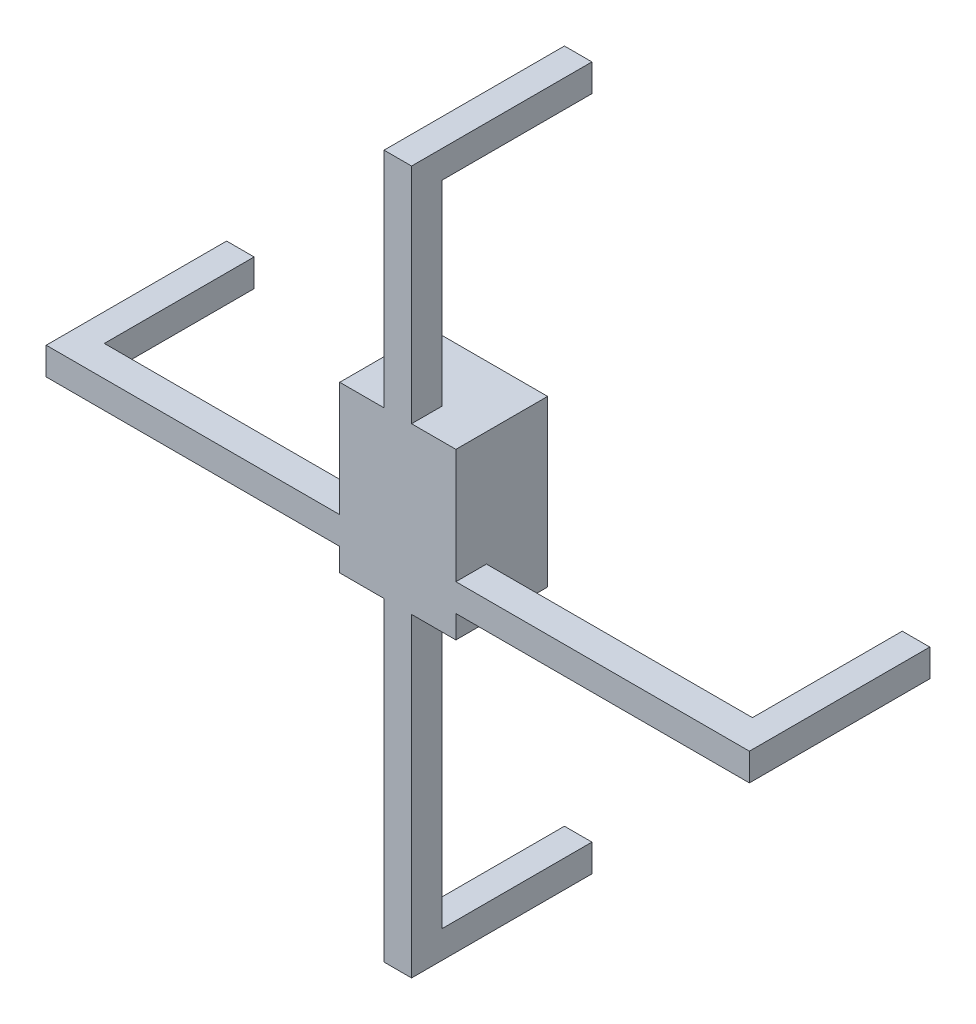
SolidWorks part; units mm, degrees
ref_plane "Front Plane" through (0, 0, 0) normal (0, 0, 1) x (1, 0, 0)
ref_plane "Top Plane" through (0, 0, 0) normal (0, 1, 0) x (1, 0, 0)
ref_plane "Right Plane" through (0, 0, 0) normal (1, 0, 0) x (0, 0, -1)
sketch "Sketch6" plane through (0, 0, 0) normal (1, 0, 0) x (0, 0, -1)
  line L0 (-4, 2.5) -> (1, 2.5) construction
  line L1 (27.5, 55.5) -> (1, 55.5)
  line L3 (-4, -55) -> (27.5, -55)
  line L4 (27.5, -55) -> (27.5, -50.5)
  line L5 (27.5, -50.5) -> (1, -50.5)
  line L8 (27.5, 60) -> (27.5, 55.5)
  line L10 (1, -50.5) -> (1, 55.5)
  line L12 (-4, -55) -> (-4, 60)
  line L22 (-4, 60) -> (27.5, 60)
  dimension "D3" = 5
  dimension "D6" = 4.5
ref_plane "Plane2" through (0, 2.5, 0) normal (0, 1, 0) x (1, 0, 0)
sketch "Sketch8" plane through (0, 2.5, 0) normal (0, 1, 0) x (1, 0, 0)
  line L0 (-57.5, -4) -> (57.5, -4)
  line L1 (-53, 1) -> (53, 1)
  line L3 (57.5, -4) -> (57.5, 27.5)
  line L11 (53, 27.5) -> (57.5, 27.5)
  line L12 (0, -4) -> (0, 1) construction
  line L13 (53, 27.5) -> (53, 1)
  line L14 (-53, 27.5) -> (-53, 1)
  line L15 (-53, 27.5) -> (-57.5, 27.5)
  line L16 (-57.5, -4) -> (-57.5, 27.5)
  point P0 (10.2551, -12.9586)
  point P2 (-10.2551, -12.9586)
  dimension "D2" = 4.5
  dimension "D9" = 5
extrude "Boss-Extrude7" add sketch "Sketch8" along normal blind 2.25 and the other way blind 2.25
sketch "Sketch10" plane through (0, 0, -1) normal (0, 0, -1) x (-1, 0, 0)
  line L2 (6.5, 20.5) -> (-6.5, 20.5)
  line L3 (6.5, 20.5) -> (6.5, -2.5)
  line L4 (-6.5, 20.5) -> (-6.5, -2.5)
  line L7 (6.5, -2.5) -> (6.5, -3.5)
  line L8 (-6.5, -2.5) -> (-6.5, -3.5)
  line L10 (9.5, -2.5) -> (9.5, -3.5)
  line L11 (9.5, 23.5) -> (9.5, -2.5)
  line L12 (9.5, 23.5) -> (-9.5, 23.5)
  line L13 (-9.5, 23.5) -> (-9.5, -2.5)
  line L14 (-9.5, -2.5) -> (-9.5, -3.5)
  line L15 (9.5, -3.5) -> (6.5, -3.5)
  line L16 (-9.5, -3.5) -> (-6.5, -3.5)
  point P6 (0, 1)
  dimension "D1" = 23
  dimension "D2" = 13
  dimension "D3" = 3
extrude "Boss-Extrude10" add sketch "Sketch10" along normal blind 10
extrude "Boss-Extrude12" add sketch "Sketch6" along normal blind 2.25 and the other way blind 2.25
sketch "Sketch11" plane through (0, 0, -1) normal (0, 0, 1) x (1, 0, 0)
  line L1 (-9.5, 23.5) -> (9.5, 23.5)
  line L2 (-9.5, 23.5) -> (-9.5, -3.5)
  line L3 (-9.5, -3.5) -> (9.5, -3.5)
  line L4 (9.5, 23.5) -> (9.5, -3.5)
extrude "Boss-Extrude13" add sketch "Sketch11" along normal up to surface (5 mm away) up to face at (0, 2.5, 4)
sketch "Sketch12" plane through (0, 0, -27.5) normal (0, 0, -1) x (-1, 0, 0)
  line L1 (67.1479, 86.4348) -> (-81.6769, 86.4348)
  line L2 (67.1479, 86.4348) -> (67.1479, -69.4582)
  line L3 (67.1479, -69.4582) -> (-81.6769, -69.4582)
  line L4 (-81.6769, 86.4348) -> (-81.6769, -69.4582)
extrude "Cut-Extrude1" cut sketch "Sketch12" against normal blind 2
